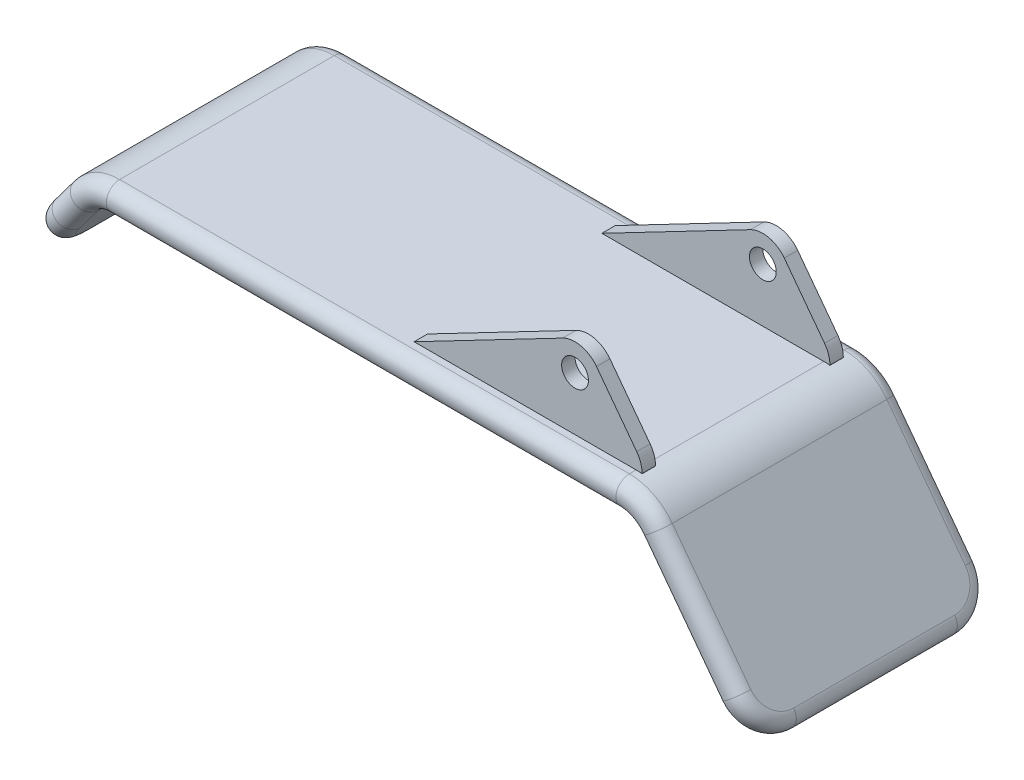
SolidWorks part; units mm, degrees
ref_plane "Front Plane" through (0, 0, 0) normal (0, 0, 1) x (1, 0, 0)
ref_plane "Top Plane" through (0, 0, 0) normal (0, 1, 0) x (1, 0, 0)
ref_plane "Right Plane" through (0, 0, 0) normal (1, 0, 0) x (0, 0, -1)
sketch "Sketch1" plane through (0, 0, 0) normal (0, 0, 1) x (1, 0, 0)
  line L0 (-19, 0) -> (19, 0)
  line L1 (20.6, -0.8) -> (28.25, -11)
  line L2 (-20.6, -0.8) -> (-23.75, -5)
  line L3 (0, 0) -> (0, -11) construction
  line L4 (-28.25, -11) -> (28.25, -11) construction
  line L5 (-23.75, -5) -> (-28.25, -11) construction
  arc A0 (-19, 0) -> (-20.6, -0.8) centre (-19, -2) ccw
  arc A1 (19, 0) -> (20.6, -0.8) centre (19, -2) cw
  point P10 (-20, 0)
  point P13 (20, 0)
  dimension "D5" = 2
  dimension "D1" = 11
  dimension "D2" = 52
  dimension "D3" = 40
  dimension "D4" = 5
extrude "Extrude-Thin1" add sketch "Sketch1" along normal mid plane 18 thin thin type one direction wall 2
fillet "Fillet1" radius 3 4 edges at (-24.55, -4.4, 9) (-24.55, -4.4, -9) (29.05, -10.4, -9) (29.05, -10.4, 9)
fillet "Fillet2" 2 edges at (0, 2, 9) (0, 0, 9) type full round first side face at (0, 2, 0) second side face at (0, 0, 0) middle face at (0.75, -1.3056, 9)
ref_plane "Plane1" through (0, 0, 7.5) normal (0, 0, 1) x (1, 0, 0)
sketch "Sketch2" plane through (0, 0, 7.5) normal (0, 0, 1) x (1, 0, 0)
  line L0 (2.45, 2) -> (13.5255, 7.7735)
  line L1 (-19, 2) -> (19, 2) construction
  line L2 (16.05, 7.2) -> (19.05, 3.2)
  line L3 (19.45, 2) -> (19.45, 1.9746)
  line L4 (2.45, 2) -> (19, 2)
  line L5 (19, 0) -> (-19, 0) construction
  arc A0 (13.5255, 7.7735) -> (16.05, 7.2) centre (14.45, 6) cw
  arc A1 (22.2, 0.4) -> (19, 2) centre (19, -2) ccw construction
  arc A2 (19.05, 3.2) -> (19.45, 2) centre (17.45, 2) cw
  arc A3 (19.45, 1.9746) -> (19, 2) centre (19, -2) ccw
  arc A4 (27.65, -10.2) -> (29.25, -9) centre (28.45, -9.6) ccw construction
  circle A5 centre (14.45, 6) radius 1
  dimension "D1" = 2
  dimension "D4" = 2
  dimension "D7" = 2
  dimension "D2" = 8
  dimension "D3" = 14
  dimension "D5" = 12
  dimension "D6" = 17
extrude "Extrude1" add sketch "Sketch2" against normal blind 1
mirror "Mirror1" about plane through (0, 0, 0) normal (0, 0, 1) of "Extrude1"
